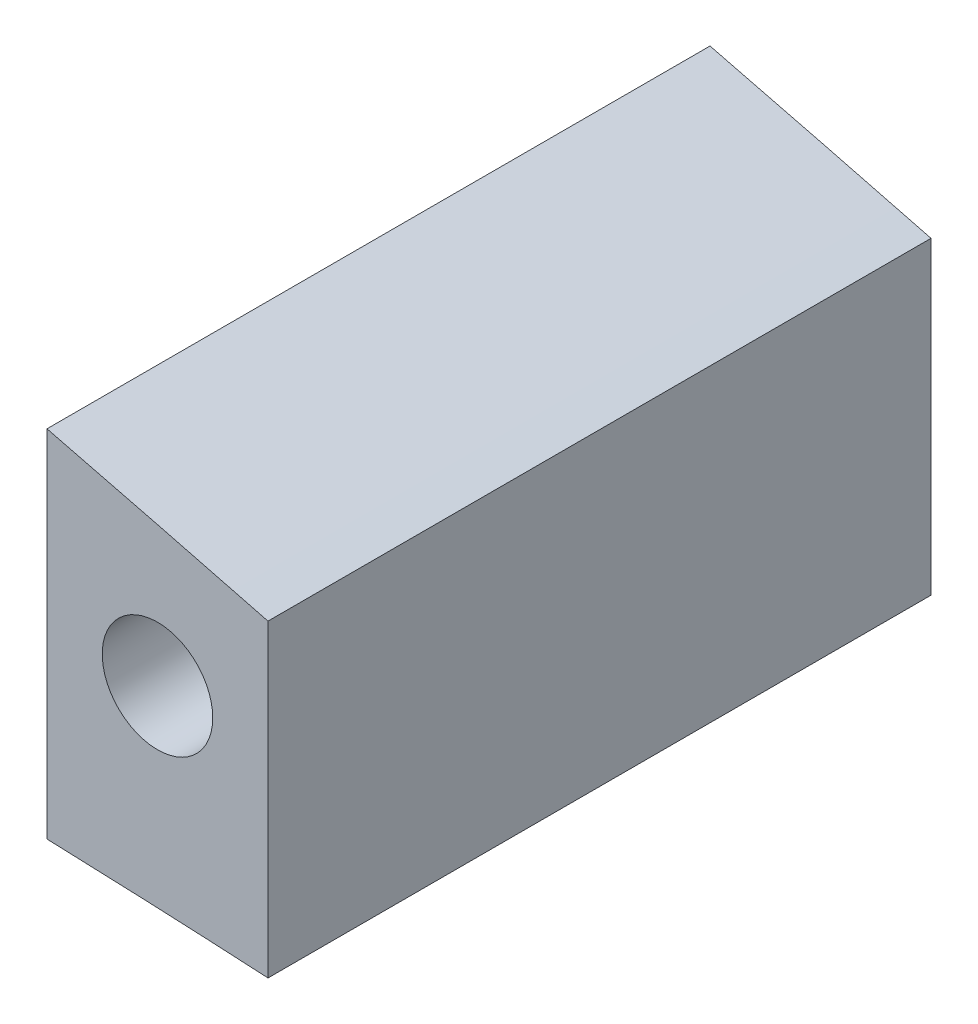
SolidWorks part; units mm, degrees
ref_plane "Front Plane" through (0, 0, 0) normal (0, 0, 1) x (1, 0, 0)
ref_plane "Top Plane" through (0, 0, 0) normal (0, 1, 0) x (1, 0, 0)
ref_plane "Right Plane" through (0, 0, 0) normal (1, 0, 0) x (0, 0, -1)
sketch "Sketch1" plane through (0, 0, 0) normal (0, 0, 1) x (1, 0, 0)
  spline S0 degree 3 poles (0.0006, 0.0001) (0.8106, 7.3592) (8.6491, 17.8566) (26.2867, 29.9752) (52.1111, 42.0692) (89.5976, 49.2908) (131.4008, 47.8848) (173.2567, 40.0411) (217.9611, 29.613) (256.9521, 19.5289) (290.3598, 8.711) (301.2732, 4.3828) (314.8169, -0.5162) (309.8463, 0.0001) knots 0 0 0 0 0.060864 0.113688 0.188609 0.312909 0.448482 0.557612 0.691544 0.852438 0.929756 0.976058 1 1 1 1
  spline S1 degree 3 poles (309.8463, 0.0001) (303.9568, 1.471) (293.9895, 2.094) (276.264, 4.5144) (260.8463, 5.4274) (235.8588, 7.8703) (205.1014, 8.8381) (157.7186, 9.0307) (110.4973, 6.1815) (66.5062, -0.5867) (36.4547, -6.0985) (15.3166, -6.1891) (1.2307, -6.9241) (0.0006, 0.0001) knots 0 0 0 0 0.057787 0.095275 0.171021 0.205339 0.335319 0.464904 0.658702 0.785512 0.893517 0.943092 1 1 1 1
extrude "Boss-Extrude1" add sketch "Sketch1" along normal blind 38.1
sketch "Sketch2" plane through (0, 0, 38.1) normal (0, 0, 1) x (1, 0, 0)
  circle A0 centre (20.32, 10.16) radius 6.35
  circle A1 centre (227.2963, 19.0501) radius 3.175
  dimension "D2" = 12.7
  dimension "D3" = 6.35
  dimension "D6" = 20.32
  dimension "D1" = 82.55
  dimension "D4" = 19.05
  dimension "D5" = 10.16
extrude "Cut-Extrude1" cut sketch "Sketch2" against normal through all
sketch "Sketch3" plane through (0, 0, 38.1) normal (0, 0, 1) x (1, 0, 0)
  line L1 (350.4863, -6.3499) -> (233.6463, -6.3499)
  line L2 (350.4863, -6.3499) -> (350.4863, 44.4501)
  line L3 (350.4863, 44.4501) -> (233.6463, 44.4501)
  line L4 (233.6463, -6.3499) -> (233.6463, 44.4501)
  circle A0 centre (227.2963, 19.0501) radius 3.175 construction
  dimension "D1" = 6.35
  dimension "D2" = 116.84
  dimension "D3" = 50.8
  dimension "D4" = 44.45
extrude "Cut-Extrude2" cut sketch "Sketch3" against normal through all contours L3 L4 L1 L2
sketch "Sketch4" plane through (0, 0, 38.1) normal (0, 0, 1) x (1, 0, 0)
  line L0 (233.6463, 7.6905) -> (233.6463, 25.4528) construction
  line L1 (220.9463, -24.2166) -> (-29.2042, -24.2166)
  line L2 (220.9463, -24.2166) -> (220.9463, 93.2727)
  line L3 (220.9463, 93.2727) -> (-29.2042, 93.2727)
  line L4 (-29.2042, -24.2166) -> (-29.2042, 93.2727)
  dimension "D1" = 12.7
extrude "Cut-Extrude3" cut sketch "Sketch4" against normal through all
